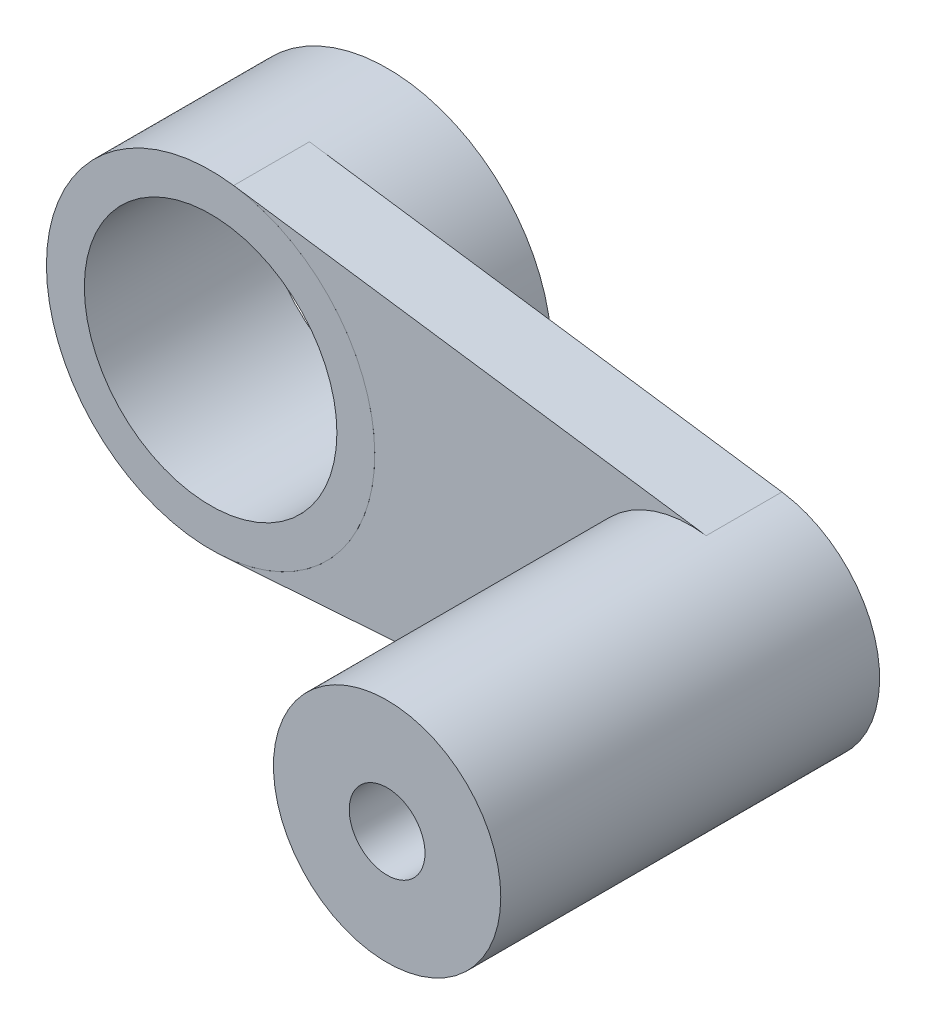
SolidWorks part; units mm, degrees
material "Acero galvanizado"
ref_plane "Alzado" through (0, 0, 0) normal (0, 0, 1) x (1, 0, 0)
ref_plane "Planta" through (0, 0, 0) normal (0, 1, 0) x (1, 0, 0)
ref_plane "Vista lateral" through (0, 0, 0) normal (1, 0, 0) x (0, 0, -1)
sketch "Croquis1" plane through (0, 0, 0) normal (0, 0, 1) x (1, 0, 0)
  line L0 (2.3809, 29.7103) -> (39.7955, 24.4046)
  line L1 (1.4656, 3.8709) -> (39.1618, 6.5158)
  line L2 (41.5319, 15.4938) -> (47.5319, 15.4938) construction
  circle A1 centre (0.5557, 16.839) radius 10
  circle A5 centre (0.5557, 16.839) radius 13
  circle A6 centre (38.5319, 15.4938) radius 3
  circle A8 centre (38.5319, 15.4938) radius 9
  point P12 (0, 0)
  point P13 (0, 0)
  point P14 (47.5319, 15.4938)
  point P15 (39.7955, 24.4046)
  point P16 (0, 0)
  point P17 (0, 0)
  point P18 (0, 0)
  point P19 (39.7956, 24.4046)
  point P20 (39.7955, 24.4046)
  point P21 (0, 0)
  dimension "D1" = 6
  dimension "D2" = 20
  dimension "D3" = 6
  dimension "D4" = 38
  dimension "D5" = 26
extrude "Saliente-Extruir1" add sketch "Croquis1" along normal blind 24 contours A8 A6 region at (45.1357, 21.2272, 0)
extrude "Saliente-Extruir2" add sketch "Croquis1<4>" against normal blind 14 separate body contours A5 A1 region at (10.0946, 25.1207, 0)
sketch "Croquis1<4>" plane through (0, 0, 0) normal (0, 0, 1) x (1, 0, 0) same geometry as "Croquis1"
extrude "Saliente-Extruir5" add sketch "Croquis1<11>" against normal blind 6 contours A8 L0 A5 L1 | A6 A8 region at (21.0643, 16.1125, 0) region at (45.1357, 21.2272, 0)
sketch "Croquis1<11>" plane through (0, 0, 0) normal (0, 0, 1) x (1, 0, 0) same geometry as "Croquis1"
